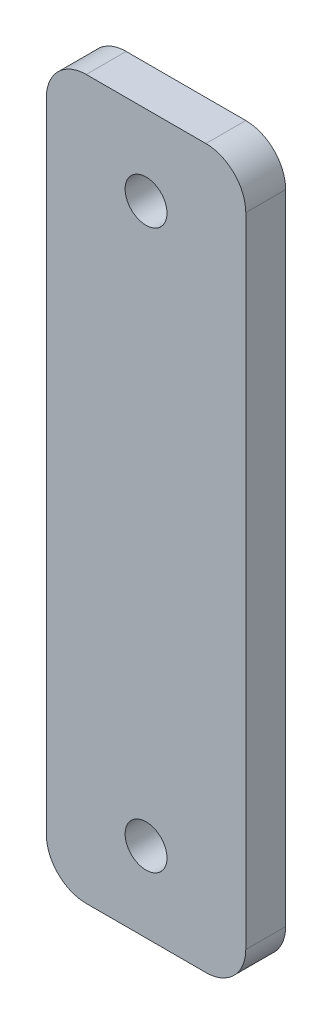
SolidWorks part; units mm, degrees
material "1.4003 (X2CrNi12)"
ref_plane "Ön Düzlem" through (0, 0, 0) normal (0, 0, 1) x (1, 0, 0)
ref_plane "Üst Düzlem" through (0, 0, 0) normal (0, 1, 0) x (1, 0, 0)
ref_plane "Sağ Düzlem" through (0, 0, 0) normal (1, 0, 0) x (0, 0, -1)
sketch "Çizim1" plane through (0, 0, 0) normal (0, 0, 1) x (1, 0, 0)
  line L1 (-25, 90) -> (25, 90)
  line L2 (-25, 90) -> (-25, -90)
  line L3 (-25, -90) -> (25, -90)
  line L4 (25, 90) -> (25, -90)
  line L5 (-25, 90) -> (25, -90) construction
  line L6 (-25, -90) -> (25, 90) construction
  point P0 (0, 0)
  dimension "D1" = 50
  dimension "D2" = 180
base flange "Taban-Flanş1" sketch "Çizim1" thickness 10 reverse thickness direction no parameters "D1"=5
fillet "Radyus1" radius 10 4 edges at (-25, 90, -5) (25, 90, -5) (25, -90, -5) (-25, -90, -5)
sketch "Çizim2" plane through (0, 0, 0) normal (0, 0, 1) x (1, 0, 0)
  circle A4 centre (0, 70) radius 5.25
  circle A5 centre (0, -70) radius 5.25
  dimension "D3" = 70
  dimension "D1" = 10.5
  dimension "D2" = 70
extrude "Kes-Ekstrüzyon1" cut sketch "Çizim2" against normal blind 20
sketch "Büküm-Çizgileri1" [suppressed] plane through (0, 0, 0) normal (0, 1, 0) x (1, 0, 0)
sketch "Sınırlandırma-Kutusu1" [suppressed] plane through (0, 0, 0) normal (0, 1, 0) x (1, 0, 0)
sheet metal parameters "Sac-Levha1" thickness 10 parameters "D1"=5
flat pattern "Düz-Çoğaltma1" [suppressed]
sketch "Büküm-Çizgileri2" plane through (0, 0, 0) normal (0, 1, 0) x (1, 0, 0)
sketch3d "Sınırlandırma-Kutusu2" [suppressed]
  line L0 (40, 70, 0) -> (40, -70, 0) construction
  line L1 (-40, 70, 0) -> (-40, -70, 0) construction
  line L2 (40, 70, 0) -> (-40, 70, 0) construction
  line L3 (40, -70, 0) -> (-40, -70, 0) construction
sheet metal parameters "Sac-Levha2" thickness 10 parameters "D1"=5
flat pattern "Düz-Çoğaltma1"
sketch "Büküm-Çizgileri2" plane through (0, 0, 0) normal (0, 1, 0) x (1, 0, 0)
sketch3d "Sınırlandırma-Kutusu2" [suppressed]
  line L0 (25, 90, 0) -> (25, -90, 0) construction
  line L1 (-25, 90, 0) -> (-25, -90, 0) construction
  line L2 (25, 90, 0) -> (-25, 90, 0) construction
  line L3 (25, -90, 0) -> (-25, -90, 0) construction
